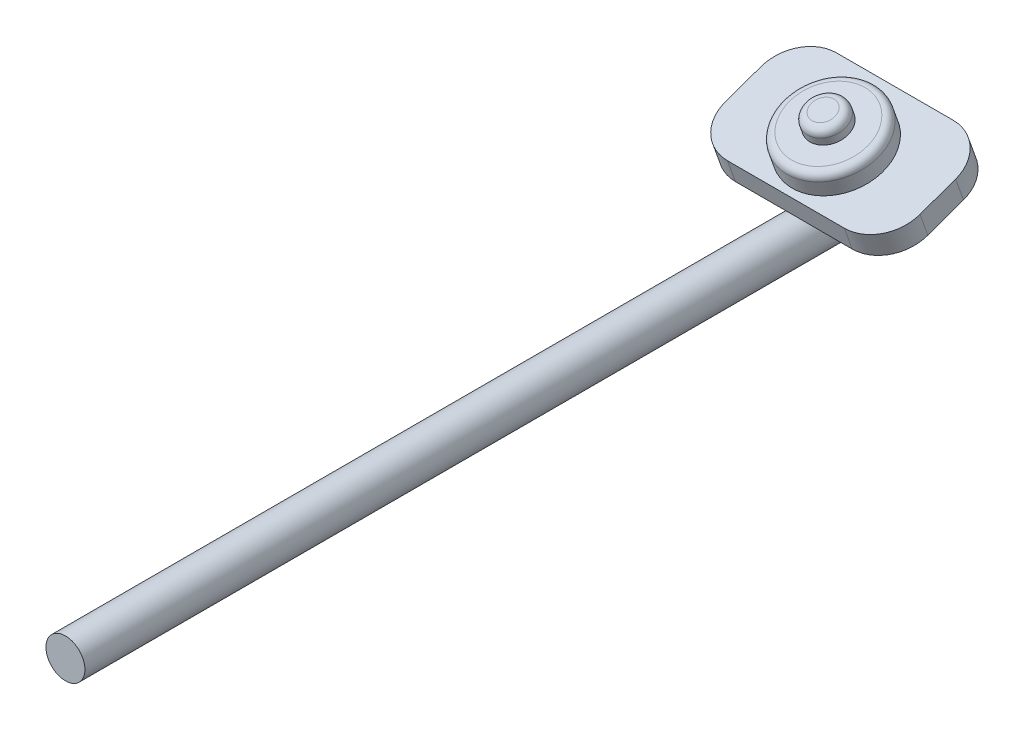
SolidWorks part; units mm, degrees
ref_plane "前视基准面" through (0, 0, 0) normal (0, 0, 1) x (1, 0, 0)
ref_plane "上视基准面" through (0, 0, 0) normal (0, 1, 0) x (1, 0, 0)
ref_plane "右视基准面" through (0, 0, 0) normal (1, 0, 0) x (0, 0, -1)
other "Configuration Table"
sketch "草图1" plane through (0, 0, 0) normal (0, 0, 1) x (1, 0, 0)
  circle A0 centre (0, 0) radius 2.5
  dimension "D1" = 5
extrude "凸台-拉伸1" add sketch "草图1" along normal blind 100
sketch "草图2" plane through (0, 0, 0) normal (0, 1, 0) x (1, 0, 0)
  line L1 (-12.5, -7.5) -> (12.5, -7.5)
  line L2 (-12.5, -7.5) -> (-12.5, 7.5)
  line L3 (-12.5, 7.5) -> (12.5, 7.5)
  line L4 (12.5, -7.5) -> (12.5, 7.5)
  point P4 (0, -7.5)
  dimension "D1" = 15
  dimension "D2" = 25
  dimension "D3" = 7.5
extrude "凸台-拉伸2" add sketch "草图2" along normal blind 15
sketch "草图4" plane through (-12.5, 0, 0) normal (-1, 0, 0) x (0, 0, 1)
  line L0 (-7.5, 7.5) -> (7.5, 2.1392)
  line L1 (-7.5, 10.6858) -> (7.5, 5.325)
  line L2 (7.5, 15) -> (7.5, 0) construction
  line L3 (-7.5, 7.5) -> (-6.4904, 10.325)
  line L4 (-7.5, 0) -> (7.5, 0)
  line L5 (7.5, 0) -> (7.5, 15)
  line L6 (7.5, 15) -> (-7.5, 15)
  line L7 (-7.5, 15) -> (-7.5, 0)
  line L8 (-7.5, 0) -> (7.5, 0)
  line L9 (7.5, 0) -> (7.5, 15)
  line L10 (7.5, 15) -> (-7.5, 15)
  line L11 (-7.5, 15) -> (-7.5, 0)
  line L12 (7.5, 5.325) -> (6.4904, 2.5)
  line M7 (-7.5, 0) -> (7.5, 0)
  line M8 (7.5, 0) -> (7.5, 15)
  line M9 (7.5, 15) -> (-7.5, 15)
  line M10 (-7.5, 15) -> (-7.5, 0)
  dimension "D2" = 2.5
  dimension "D3" = 3
  dimension "D1" = 0
extrude "切除-拉伸1" cut sketch "草图4" against normal through all contours L12 L0 M8 | L1 M10 M8 M9 | L3 L1 M10 region at (-12.5, 9.5036, -7.1635) region at (-12.5, 3.3214, 7.1635) region at (-12.5, 11.3315, 0.958)
extrude "切除-拉伸3" cut sketch "草图4<3>" against normal through all contours L0 M10 M7 M8 region at (-12.5, 2.6582, -1.3904)
sketch "草图4<3>" plane through (-12.5, 0, 0) normal (-1, 0, 0) x (0, 0, 1) same geometry as "草图4"
extrude "凸台-拉伸3" add sketch "草图1<2>" along normal blind 20
sketch "草图1<2>" plane through (0, 0, 0) normal (0, 0, 1) x (1, 0, 0) same geometry as "草图1"
sketch "草图5" plane through (0, 7.0987, 2.537) normal (0, 0.9417, 0.3365) x (1, 0, 0)
  line L4 (-12.5, 9.5866) -> (-12.5, -5.2704)
  line L5 (-12.5, -5.2704) -> (12.5, -5.2704)
  line L6 (12.5, -5.2704) -> (12.5, 9.5866)
  line L7 (12.5, 9.5866) -> (-12.5, 9.5866)
  line L8 (-12.5, 9.5866) -> (-12.5, -5.2704)
  line L9 (-12.5, -5.2704) -> (12.5, -5.2704)
  line L10 (12.5, -5.2704) -> (12.5, 9.5866)
  line L11 (12.5, 9.5866) -> (-12.5, 9.5866)
  circle A0 centre (0, 1.5866) radius 6
  circle A1 centre (0, 1.5866) radius 2.5
  dimension "D1" = 12
  dimension "D5" = 5
  dimension "D3" = 12.5
  dimension "D4" = 8
  dimension "D2" = 0
extrude "凸台-拉伸4" add sketch "草图5" along normal blind 3 contours A0 A1 | A1 region at (-5.8303, 7.6327, 1.043) region at (0, 7.6327, 1.043)
extrude "凸台-拉伸5" add sketch "草图5<3>" along normal blind 5 contours A1 region at (0, 7.6327, 1.043)
sketch "草图5<3>" plane through (0, 7.0987, 2.537) normal (0, 0.9417, 0.3365) x (1, 0, 0) same geometry as "草图5"
fillet "圆角1" radius 5 4 edges at (12.5, 8.9125, -6.9952) (12.5, 3.9125, 6.9952) (-12.5, 8.9125, -6.9952) (-12.5, 3.9125, 6.9952)
fillet "圆角2" radius 1 1 edges at (0, 8.4384, 7.7026)
fillet "圆角3" radius 1 1 edges at (0, 11.4997, 5.0799)
